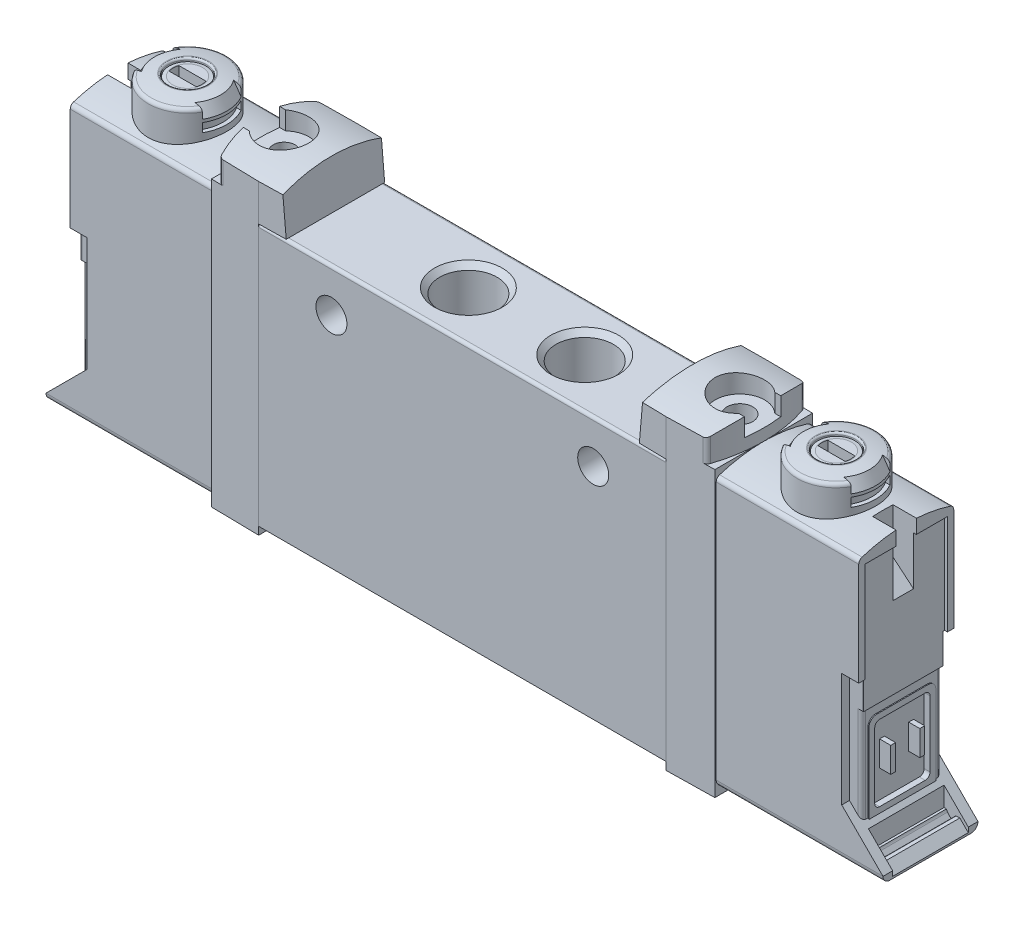
SolidWorks part; units mm, degrees
ref_plane "Front Plane" through (0, 0, 0) normal (0, 0, 1) x (1, 0, 0)
ref_plane "Top Plane" through (0, 0, 0) normal (0, 1, 0) x (1, 0, 0)
ref_plane "Right Plane" through (0, 0, 0) normal (1, 0, 0) x (0, 0, -1)
sketch "Sketch1" plane through (0, 0, 0) normal (1, 0, 0) x (0, 0, -1)
  line L0 (-5.125, 0) -> (5.125, 0)
  line L1 (5.125, 0) -> (5.125, 26.7)
  line L2 (4.825, 27) -> (-4.825, 27)
  line L3 (-5.125, 26.7) -> (-5.125, 0)
  arc A0 (5.125, 26.7) -> (4.825, 27) centre (4.825, 26.7) ccw
  arc A1 (-4.825, 27) -> (-5.125, 26.7) centre (-4.825, 26.7) ccw
extrude "Boss-Extrude1" add sketch "Sketch1" against normal blind 21 and the other way blind 21
sketch "Sketch2" plane through (0, 0, 0) normal (0, 0, 1) x (1, 0, 0)
  circle A0 centre (13.5, 22.6) radius 1.6
extrude "Cut-Extrude1" cut sketch "Sketch2" along normal blind 6 and the other way blind 6
sketch "Sketch3" plane through (0, 0, 0) normal (0, 0, 1) x (1, 0, 0)
  circle A0 centre (-13.5, 22.6) radius 1.6
extrude "Cut-Extrude2" cut sketch "Sketch3" along normal blind 6 and the other way blind 6
ref_plane "Plane1" through (0, 0, -0.005) normal (0, 0, 1) x (1, 0, 0)
ref_plane "Plane2" through (0, 0, -1.555) normal (0, 0, 1) x (1, 0, 0)
ref_plane "Plane3" through (0, 0, 1.545) normal (0, 0, 1) x (1, 0, 0)
ref_plane "Plane4" through (0, 0, 1.495) normal (0, 0, 1) x (1, 0, 0)
ref_plane "Plane5" through (0, 0, -2.205) normal (0, 0, 1) x (1, 0, 0)
sketch "Sketch4" plane through (0, 0, -0.005) normal (0, 0, 1) x (1, 0, 0)
  line L0 (12.5, 13.5) -> (14.6, 13.5)
  line L1 (14.6, 13.5) -> (14.6, 6.8)
  line L2 (14.6, 6.8) -> (15.4585, 6.8)
  line L3 (15.4585, 6.8) -> (15.4585, 0.5415)
  line L4 (15.4585, 0.5415) -> (16, 0)
  line L5 (16, 0) -> (12.5, 0)
  line L6 (12.5, 0) -> (12.5, 13.5)
  line L7 (12.5, 0) -> (12.5, 13.5) construction
sketch "Sketch5" plane through (0, 0, -0.005) normal (0, 0, 1) x (1, 0, 0)
  line L0 (1.5, 20.0124) -> (3.6, 18.8)
  line L1 (3.6, 18.8) -> (3.6, 6.8)
  line L2 (3.6, 6.8) -> (4.4585, 6.8)
  line L3 (4.4585, 6.8) -> (4.4585, 0.5415)
  line L4 (4.4585, 0.5415) -> (5, 0)
  line L5 (5, 0) -> (1.5, 0)
  line L6 (1.5, 0) -> (1.5, 20.0124)
  line L7 (1.5, 0) -> (1.5, 20.0124) construction
sketch "Sketch6" plane through (0, 0, -0.005) normal (0, 0, 1) x (1, 0, 0)
  line L0 (-9.5, 13.5) -> (-7.4, 13.5)
  line L1 (-7.4, 13.5) -> (-7.4, 6.8)
  line L2 (-7.4, 6.8) -> (-6.5415, 6.8)
  line L3 (-6.5415, 6.8) -> (-6.5415, 0.5415)
  line L4 (-6.5415, 0.5415) -> (-6, 0)
  line L5 (-6, 0) -> (-9.5, 0)
  line L6 (-9.5, 0) -> (-9.5, 13.5)
  line L7 (-9.5, 0) -> (-9.5, 13.5) construction
revolve "Cut-Revolve1" cut sketch "Sketch4" angle 360 about L7 reverse direction yes
cosmetic thread "Cosmetic Thread1" parameters "D1"=6, "D2"=7
revolve "Cut-Revolve2" cut sketch "Sketch5" angle 360 about L7 reverse direction yes
cosmetic thread "Cosmetic Thread2" parameters "D1"=6, "D2"=7
revolve "Cut-Revolve3" cut sketch "Sketch6" angle 360 about L7 reverse direction yes
cosmetic thread "Cosmetic Thread3" parameters "D1"=6, "D2"=7
hole_wizard "Hole1" positions "Sketch8" profile "Sketch7" legacy
sketch "Sketch8" plane through (0, 27, 0) normal (0, 1, 0) x (-1, 0, 0)
  point P0 (4.5, 0)
sketch "Sketch7" plane through (-4.5, 27, 0) normal (1, 0, 0) x (0, 0, 1)
  line L0 (0, 0) -> (0, 6.8)
  line L1 (0, 6.8) -> (2.9585, 6.8)
  line L2 (2.9585, 6.8) -> (2.9585, 0.5415)
  line L3 (2.9585, 0.5415) -> (3.5, 0)
  line L4 (3.5, 0) -> (0, 0)
  line L5 (0, -6.4453) -> (0, 115.525) construction
  line L6 (-2.9585, 0.5415) -> (-3.5, 0) construction
  dimension "Diameter" = 5.917
  dimension "Depth" = 6.8
  dimension "C-Sink Angle" = 90
  dimension "C-Sink Diameter" = 7
cosmetic thread "Cosmetic Thread4" parameters "D1"=6, "D2"=7
hole_wizard "Hole2" positions "Sketch10" profile "Sketch9" legacy
sketch "Sketch10" plane through (0, 27, 0) normal (0, 1, 0) x (-1, 0, 0)
  point P0 (-7.5, 0)
sketch "Sketch9" plane through (7.5, 27, 0) normal (1, 0, 0) x (0, 0, 1)
  line L0 (0, 0) -> (0, 6.8)
  line L1 (0, 6.8) -> (2.9585, 6.8)
  line L2 (2.9585, 6.8) -> (2.9585, 0.5415)
  line L3 (2.9585, 0.5415) -> (3.5, 0)
  line L4 (3.5, 0) -> (0, 0)
  line L5 (0, -6.4453) -> (0, 115.525) construction
  line L6 (-2.9585, 0.5415) -> (-3.5, 0) construction
  dimension "Diameter" = 5.917
  dimension "Depth" = 6.8
  dimension "C-Sink Angle" = 90
  dimension "C-Sink Diameter" = 7
cosmetic thread "Cosmetic Thread5" parameters "D1"=6, "D2"=7
ref_plane "Plane6" through (0, 20.2, 0) normal (0, 1, 0) x (-1, 0, 0)
hole_wizard "Hole3" positions "Sketch12" profile "Sketch11" legacy
sketch "Sketch12" plane through (0, 20.2, 0) normal (0, 1, 0) x (-1, 0, 0)
  point P0 (4.5, 1)
sketch "Sketch11" plane through (-4.5, 20.2, 1) normal (1, 0, 0) x (0, 0, 1)
  line L0 (0, 0) -> (0, 6.7)
  line L1 (0, 6.7) -> (1.5, 6.7)
  line L2 (1.5, 6.7) -> (1.5, 0)
  line L3 (1.5, 0) -> (0, 0)
  line L4 (0, 110) -> (0, -10) construction
  dimension "Diameter" = 3
  dimension "Depth" = 6.7
hole_wizard "Hole4" positions "Sketch14" profile "Sketch13" legacy
sketch "Sketch14" plane through (0, 20.2, 0) normal (0, 1, 0) x (-1, 0, 0)
  point P0 (-7.5, -1)
sketch "Sketch13" plane through (7.5, 20.2, -1) normal (1, 0, 0) x (0, 0, 1)
  line L0 (0, 0) -> (0, 6.7)
  line L1 (0, 6.7) -> (1.5, 6.7)
  line L2 (1.5, 6.7) -> (1.5, 0)
  line L3 (1.5, 0) -> (0, 0)
  line L4 (0, 110) -> (0, -10) construction
  dimension "Diameter" = 3
  dimension "Depth" = 6.7
ref_plane "Plane7" through (-15.16, 0, 0) normal (1, 0, 0) x (0, 0, -1)
ref_plane "Plane8" through (-8.25, 0, 0) normal (1, 0, 0) x (0, 0, -1)
ref_plane "Plane9" through (-0.95, 0, 0) normal (1, 0, 0) x (0, 0, -1)
ref_plane "Plane10" through (0, -0.8, 0) normal (0, 1, 0) x (-1, 0, 0)
sketch "Sketch15" plane through (0, -0.8, 0) normal (0, 1, 0) x (-1, 0, 0)
  line L0 (-21, 5.125) -> (-25.96, 5.0384)
  line L1 (-25.96, 5.0384) -> (-25.96, -5.0384)
  line L2 (-25.96, -5.0384) -> (-21, -5.125)
  line L3 (-21, -5.125) -> (-21, 5.125)
extrude "Boss-Extrude2" add sketch "Sketch15" along normal blind 32.5
ref_plane "Plane11" through (0, 27, 0) normal (0, 1, 0) x (-1, 0, 0)
sketch "Sketch16" plane through (0, 27, 0) normal (0, 1, 0) x (-1, 0, 0)
  line L0 (-18.21, 5.0763) -> (-21, 5.125)
  line L1 (-21, 5.125) -> (-21, -5.125)
  line L2 (-21, -5.125) -> (-18.21, -5.0763)
  line L3 (-18.21, -5.0763) -> (-18.21, 5.0763)
extrude "Boss-Extrude3" add sketch "Sketch16" along normal blind 4.7
sketch "Sketch17" plane through (0, 0, 0) normal (1, 0, 0) x (0, 0, -1)
  line L0 (-5.125, 37) -> (-5.125, 30.7973)
  line L1 (5.125, 30.7973) -> (5.125, 37)
  line L2 (5.125, 37) -> (-5.125, 37)
  arc A0 (-5.125, 30.7973) -> (5.125, 30.7973) centre (0, 16.7) cw
ref_plane "Plane12" through (0, 28.5, 0) normal (0, 1, 0) x (-1, 0, 0)
sketch "Sketch18" plane through (0, 28.5, 0) normal (0, 1, 0) x (-1, 0, 0)
  line L0 (-21, 5.125) -> (-21, 6.125)
  line L1 (-21, 6.125) -> (-31, 6.125)
  line L2 (-31, 6.125) -> (-31, -6.125)
  line L3 (-31, -6.125) -> (-21, -6.125)
  line L4 (-21, -6.125) -> (-21, -5.125)
  line L5 (-21, -5.125) -> (-24.7331, -5.0598)
  line L6 (-24.7331, 5.0598) -> (-21, 5.125)
  arc A0 (-24.7331, -5.0598) -> (-25.199, -4.7172) centre (-24.7243, -4.5599) cw
  arc A1 (-25.199, -4.7172) -> (-25.199, 4.7172) centre (-10.96, 0) cw
  arc A2 (-25.199, 4.7172) -> (-24.7331, 5.0598) centre (-24.7243, 4.5599) cw
extrude "Cut-Extrude3" cut sketch "Sketch18" along normal blind 5
sketch "Sketch19" plane through (0, 0, 0) normal (0, 0, 1) x (1, 0, 0)
  line L0 (13.21, 27) -> (18.21, 27)
  line L1 (18.21, 27) -> (18.6474, 32)
  line L2 (18.6474, 32) -> (13.21, 32)
  line L3 (13.21, 32) -> (13.21, 27)
extrude "Cut-Extrude4" cut sketch "Sketch19" along normal blind 6 and the other way blind 6
ref_plane "Plane13" through (25.96, 0, 0) normal (1, 0, 0) x (0, 0, -1)
sketch "Sketch20" plane through (25.96, 0, 0) normal (1, 0, 0) x (0, 0, -1)
  line L0 (-4.9, 27.3163) -> (-4.9, 0.7)
  line L1 (-4.2, 0) -> (4.2, 0)
  line L2 (4.9, 0.7) -> (4.9, 27.3163)
  arc A0 (-4.9, 0.7) -> (-4.2, 0) centre (-4.2, 0.7) ccw
  arc A1 (4.2, 0) -> (4.9, 0.7) centre (4.2, 0.7) ccw
  arc A2 (4.9, 27.3163) -> (4.5517, 27.7927) centre (4.4, 27.3163) ccw
  arc A3 (4.5517, 27.7927) -> (-4.5517, 27.7927) centre (0, 13.5) ccw
  arc A4 (-4.5517, 27.7927) -> (-4.9, 27.3163) centre (-4.4, 27.3163) ccw
extrude "Boss-Extrude4" add sketch "Sketch20" along normal blind 17.2
sketch "Sketch21" plane through (0, 0, 0) normal (0, 0, 1) x (1, 0, 0)
  line L0 (38.9067, 16.7) -> (38.9067, 4.9533)
  line L1 (38.9067, 4.9533) -> (43.16, 0.7)
  line L2 (43.16, 0.7) -> (43.16, 30)
  line L3 (43.16, 30) -> (40.66, 30)
  line L4 (40.66, 30) -> (40.66, 16.7)
  line L5 (40.66, 16.7) -> (38.9067, 16.7)
extrude "Cut-Extrude5" cut sketch "Sketch21" along normal blind 6 and the other way blind 6
ref_plane "Plane14" through (0, 13.6, 0) normal (0, 1, 0) x (-1, 0, 0)
sketch "Sketch22" plane through (0, 13.6, 0) normal (0, 1, 0) x (-1, 0, 0)
  line L0 (-38.16, 4.1) -> (-39.76, 4.1)
  line L1 (-40.16, 3.7) -> (-40.16, -3.7)
  line L2 (-39.76, -4.1) -> (-38.16, -4.1)
  line L3 (-38.16, -4.1) -> (-38.16, 4.1)
  arc A0 (-39.76, 4.1) -> (-40.16, 3.7) centre (-39.76, 3.7) ccw
  arc A1 (-40.16, -3.7) -> (-39.76, -4.1) centre (-39.76, -3.7) ccw
extrude "Boss-Extrude5" add sketch "Sketch22" against normal blind 12
sketch "Sketch23" plane through (0, 13.6, 0) normal (0, 1, 0) x (-1, 0, 0)
  line L0 (-37.66, 4.1) -> (-40.26, 4.1)
  line L1 (-40.66, 3.7) -> (-40.66, -3.7)
  line L2 (-40.26, -4.1) -> (-37.66, -4.1)
  line L3 (-37.66, -4.1) -> (-37.66, 4.1)
  arc A0 (-40.26, 4.1) -> (-40.66, 3.7) centre (-40.26, 3.7) ccw
  arc A1 (-40.66, -3.7) -> (-40.26, -4.1) centre (-40.26, -3.7) ccw
extrude "Boss-Extrude6" add sketch "Sketch23" along normal blind 3.1
ref_plane "Plane15" through (40.16, 0, 0) normal (1, 0, 0) x (0, 0, -1)
sketch "Sketch24" plane through (40.16, 0, 0) normal (1, 0, 0) x (0, 0, -1)
  line L0 (-3.45, 0) -> (3.45, 0)
  line L1 (3.45, 0) -> (3.45, 11.8)
  line L2 (2.65, 12.6) -> (-2.65, 12.6)
  line L3 (-3.45, 11.8) -> (-3.45, 0)
  arc A0 (3.45, 11.8) -> (2.65, 12.6) centre (2.65, 11.8) ccw
  arc A1 (-2.65, 12.6) -> (-3.45, 11.8) centre (-2.65, 11.8) ccw
extrude "Boss-Extrude7" add sketch "Sketch24" along normal blind 0.1
sketch "Sketch25" plane through (40.16, 0, 0) normal (1, 0, 0) x (0, 0, -1)
  line L0 (-2.85, 11.5) -> (-2.85, 4.7)
  line L1 (-2.35, 4.2) -> (2.35, 4.2)
  line L2 (2.85, 4.7) -> (2.85, 11.5)
  line L3 (2.35, 12) -> (-2.35, 12)
  arc A0 (-2.85, 4.7) -> (-2.35, 4.2) centre (-2.35, 4.7) ccw
  arc A1 (2.35, 4.2) -> (2.85, 4.7) centre (2.35, 4.7) ccw
  arc A2 (2.85, 11.5) -> (2.35, 12) centre (2.35, 11.5) ccw
  arc A3 (-2.35, 12) -> (-2.85, 11.5) centre (-2.35, 11.5) ccw
extrude "Cut-Extrude6" cut sketch "Sketch25" along normal blind 0.5 and the other way blind 0.5
ref_plane "Plane16" through (0, 9.65, 0) normal (0, 1, 0) x (-1, 0, 0)
sketch "Sketch26" plane through (0, 9.65, 0) normal (0, 1, 0) x (-1, 0, 0)
  line L0 (-35.81, -1.75) -> (-35.81, 1.75)
  line L1 (-35.81, 1.75) -> (-40.81, 1.75)
  line L2 (-40.81, 1.75) -> (-40.81, 1.25)
  line L3 (-40.81, 1.25) -> (-36.31, 1.25)
  line L4 (-36.31, 1.25) -> (-36.31, -1.25)
  line L5 (-36.31, -1.25) -> (-40.81, -1.25)
  line L6 (-40.81, -1.25) -> (-40.81, -1.75)
  line L7 (-40.81, -1.75) -> (-35.81, -1.75)
extrude "Boss-Extrude8" add sketch "Sketch26" against normal blind 2.6
sketch "Sketch27" plane through (0, 0, 0) normal (0, 0, 1) x (1, 0, 0)
  line L0 (23.5, 29.7) -> (24.825, 29.7)
  line L1 (24.825, 29.7) -> (24.625, -0.8)
  line L2 (24.625, -0.8) -> (23.5, -0.8)
  line L3 (23.5, -0.8) -> (23.5, 29.7)
  line L4 (23.5, -0.8) -> (23.5, 29.7) construction
revolve "Cut-Revolve4" cut sketch "Sketch27" angle 360 about L4 reverse direction yes
ref_plane "Plane17" through (0, 29.7, 0) normal (0, 1, 0) x (-1, 0, 0)
sketch "Sketch28" plane through (0, 29.7, 0) normal (0, 1, 0) x (-1, 0, 0)
  line L0 (-25.2283, 1.875) -> (-27, 1.875)
  line L1 (-27, 1.875) -> (-27, -1.875)
  line L2 (-27, -1.875) -> (-25.2283, -1.875)
  arc A0 (-25.2283, -1.875) -> (-25.2283, 1.875) centre (-23.5, 0) ccw
extrude "Cut-Extrude7" cut sketch "Sketch28" along normal blind 3
ref_plane "Plane18" through (0, -0.8, 0) normal (0, 1, 0) x (-1, 0, 0)
sketch "Sketch29" plane through (0, -0.8, 0) normal (0, 1, 0) x (-1, 0, 0)
  line L0 (25.96, -5.0384) -> (25.96, 5.0384)
  line L1 (25.96, 5.0384) -> (21, 5.125)
  line L2 (21, 5.125) -> (21, -5.125)
  line L3 (21, -5.125) -> (25.96, -5.0384)
extrude "Boss-Extrude9" add sketch "Sketch29" along normal blind 32.5
sketch "Sketch30" plane through (0, 27, 0) normal (0, 1, 0) x (-1, 0, 0)
  line L0 (21, -5.125) -> (21, 5.125)
  line L1 (21, 5.125) -> (18.21, 5.0763)
  line L2 (18.21, 5.0763) -> (18.21, -5.0763)
  line L3 (18.21, -5.0763) -> (21, -5.125)
extrude "Boss-Extrude10" add sketch "Sketch30" along normal blind 4.7
extrude "Cut-Extrude8" cut sketch "Sketch17" along normal blind 32 and the other way blind 32
sketch "Sketch31" plane through (0, 29.7, 0) normal (0, 1, 0) x (-1, 0, 0)
  line L0 (27, -1.875) -> (27, 1.875)
  line L1 (27, 1.875) -> (25.2283, 1.875)
  line L2 (25.2283, -1.875) -> (27, -1.875)
  arc A0 (25.2283, 1.875) -> (25.2283, -1.875) centre (23.5, 0) ccw
extrude "Cut-Extrude9" cut sketch "Sketch31" along normal blind 2
hole_wizard "Hole5" positions "Sketch33" profile "Sketch32" legacy
sketch "Sketch33" plane through (0, 29.7, 0) normal (0, 1, 0) x (-1, 0, 0)
  point P0 (23.5, 0)
sketch "Sketch32" plane through (-23.5, 29.7, 0) normal (1, 0, 0) x (0, 0, 1)
  line L0 (0, 0) -> (0, 30.5)
  line L1 (0, 30.5) -> (1.325, 30.5)
  line L2 (1.325, 30.5) -> (1.125, 0)
  line L3 (1.125, 0) -> (0, 0)
  line L4 (0, 110) -> (0, -10) construction
  dimension "Minor Diameter" = 2.65
  dimension "Depth" = 30.5
  dimension "Major Diameter" = 2.25
sketch "Sketch34" plane through (0, 0, 0) normal (0, 0, 1) x (1, 0, 0)
  line L0 (-18.6474, 32) -> (-18.21, 27)
  line L1 (-18.21, 27) -> (-13.21, 27)
  line L2 (-13.21, 27) -> (-13.21, 32)
  line L3 (-13.21, 32) -> (-18.6474, 32)
extrude "Cut-Extrude10" cut sketch "Sketch34" along normal blind 6 and the other way blind 6
sketch "Sketch35" plane through (0, 28.5, 0) normal (0, 1, 0) x (-1, 0, 0)
  line L0 (31, -6.125) -> (31, 6.125)
  line L1 (31, 6.125) -> (21, 6.125)
  line L2 (21, 6.125) -> (21, 5.125)
  line L3 (21, 5.125) -> (24.7331, 5.0598)
  line L4 (24.7331, -5.0598) -> (21, -5.125)
  line L5 (21, -5.125) -> (21, -6.125)
  line L6 (21, -6.125) -> (31, -6.125)
  arc A0 (24.7331, 5.0598) -> (25.199, 4.7172) centre (24.7243, 4.5599) cw
  arc A1 (25.199, 4.7172) -> (25.199, -4.7172) centre (10.96, 0) cw
  arc A2 (25.199, -4.7172) -> (24.7331, -5.0598) centre (24.7243, -4.5599) cw
extrude "Cut-Extrude11" cut sketch "Sketch35" along normal blind 5
ref_plane "Plane19" through (-25.96, 0, 0) normal (1, 0, 0) x (0, 0, -1)
sketch "Sketch36" plane through (-25.96, 0, 0) normal (1, 0, 0) x (0, 0, -1)
  line L0 (-4.9, 27.3163) -> (-4.9, 0.7)
  line L1 (-4.2, 0) -> (4.2, 0)
  line L2 (4.9, 0.7) -> (4.9, 27.3163)
  arc A0 (-4.9, 0.7) -> (-4.2, 0) centre (-4.2, 0.7) ccw
  arc A1 (4.2, 0) -> (4.9, 0.7) centre (4.2, 0.7) ccw
  arc A2 (4.9, 27.3163) -> (4.5517, 27.7927) centre (4.4, 27.3163) ccw
  arc A3 (4.5517, 27.7927) -> (-4.5517, 27.7927) centre (0, 13.5) ccw
  arc A4 (-4.5517, 27.7927) -> (-4.9, 27.3163) centre (-4.4, 27.3163) ccw
extrude "Boss-Extrude11" add sketch "Sketch36" against normal blind 17.2
sketch "Sketch37" plane through (0, 0, 0) normal (0, 0, 1) x (1, 0, 0)
  line L0 (-43.16, 0.7) -> (-38.9067, 4.9533)
  line L1 (-38.9067, 4.9533) -> (-38.9067, 16.7)
  line L2 (-38.9067, 16.7) -> (-40.66, 16.7)
  line L3 (-40.66, 16.7) -> (-40.66, 30)
  line L4 (-40.66, 30) -> (-43.16, 30)
  line L5 (-43.16, 30) -> (-43.16, 0.7)
extrude "Cut-Extrude12" cut sketch "Sketch37" along normal blind 6 and the other way blind 6
sketch "Sketch38" plane through (0, 13.6, 0) normal (0, 1, 0) x (-1, 0, 0)
  line L0 (39.76, 4.1) -> (38.16, 4.1)
  line L1 (38.16, 4.1) -> (38.16, -4.1)
  line L2 (38.16, -4.1) -> (39.76, -4.1)
  line L3 (40.16, -3.7) -> (40.16, 3.7)
  arc A0 (40.16, 3.7) -> (39.76, 4.1) centre (39.76, 3.7) ccw
  arc A1 (39.76, -4.1) -> (40.16, -3.7) centre (39.76, -3.7) ccw
extrude "Boss-Extrude12" add sketch "Sketch38" against normal blind 12
sketch "Sketch39" plane through (0, 13.6, 0) normal (0, 1, 0) x (-1, 0, 0)
  line L0 (40.26, 4.1) -> (37.66, 4.1)
  line L1 (37.66, 4.1) -> (37.66, -4.1)
  line L2 (37.66, -4.1) -> (40.26, -4.1)
  line L3 (40.66, -3.7) -> (40.66, 3.7)
  arc A0 (40.66, 3.7) -> (40.26, 4.1) centre (40.26, 3.7) ccw
  arc A1 (40.26, -4.1) -> (40.66, -3.7) centre (40.26, -3.7) ccw
extrude "Boss-Extrude13" add sketch "Sketch39" along normal blind 3.1
ref_plane "Plane20" through (-40.16, 0, 0) normal (1, 0, 0) x (0, 0, -1)
sketch "Sketch40" plane through (-40.16, 0, 0) normal (1, 0, 0) x (0, 0, -1)
  line L0 (-3.45, 0) -> (3.45, 0)
  line L1 (3.45, 0) -> (3.45, 11.8)
  line L2 (2.65, 12.6) -> (-2.65, 12.6)
  line L3 (-3.45, 11.8) -> (-3.45, 0)
  arc A0 (3.45, 11.8) -> (2.65, 12.6) centre (2.65, 11.8) ccw
  arc A1 (-2.65, 12.6) -> (-3.45, 11.8) centre (-2.65, 11.8) ccw
extrude "Boss-Extrude14" add sketch "Sketch40" against normal blind 0.1
sketch "Sketch41" plane through (-40.16, 0, 0) normal (1, 0, 0) x (0, 0, -1)
  line L0 (-2.85, 11.5) -> (-2.85, 4.7)
  line L1 (-2.35, 4.2) -> (2.35, 4.2)
  line L2 (2.85, 4.7) -> (2.85, 11.5)
  line L3 (2.35, 12) -> (-2.35, 12)
  arc A0 (-2.85, 4.7) -> (-2.35, 4.2) centre (-2.35, 4.7) ccw
  arc A1 (2.35, 4.2) -> (2.85, 4.7) centre (2.35, 4.7) ccw
  arc A2 (2.85, 11.5) -> (2.35, 12) centre (2.35, 11.5) ccw
  arc A3 (-2.35, 12) -> (-2.85, 11.5) centre (-2.35, 11.5) ccw
extrude "Cut-Extrude13" cut sketch "Sketch41" along normal blind 0.5 and the other way blind 0.5
sketch "Sketch42" plane through (0, 9.65, 0) normal (0, 1, 0) x (-1, 0, 0)
  line L0 (40.81, 1.75) -> (35.81, 1.75)
  line L1 (35.81, 1.75) -> (35.81, -1.75)
  line L2 (35.81, -1.75) -> (40.81, -1.75)
  line L3 (40.81, -1.75) -> (40.81, -1.25)
  line L4 (40.81, -1.25) -> (36.31, -1.25)
  line L5 (36.31, -1.25) -> (36.31, 1.25)
  line L6 (36.31, 1.25) -> (40.81, 1.25)
  line L7 (40.81, 1.25) -> (40.81, 1.75)
extrude "Boss-Extrude15" add sketch "Sketch42" against normal blind 2.6
sketch "Sketch43" plane through (0, 0, 0) normal (0, 0, 1) x (1, 0, 0)
  line L0 (33.46, 31.665) -> (37.51, 31.665)
  line L1 (37.51, 31.665) -> (37.51, 26.365)
  line L2 (37.51, 26.365) -> (33.46, 26.365)
  line L3 (33.46, 26.365) -> (33.46, 31.665)
  line L4 (33.46, 26.365) -> (33.46, 31.665) construction
revolve "Revolve1" add sketch "Sketch43" angle 360 about L4 reverse direction yes
sketch "Sketch44" plane through (0, 0, 0) normal (0, 0, 1) x (1, 0, 0)
  line L0 (-33.46, 31.665) -> (-29.41, 31.665)
  line L1 (-29.41, 31.665) -> (-29.41, 26.365)
  line L2 (-29.41, 26.365) -> (-33.46, 26.365)
  line L3 (-33.46, 26.365) -> (-33.46, 31.665)
  line L4 (-33.46, 26.365) -> (-33.46, 31.665) construction
revolve "Revolve2" add sketch "Sketch44" angle 360 about L4 reverse direction yes
sketch "Sketch45" plane through (0, 0, 0) normal (0, 0, 1) x (1, 0, 0)
  line L0 (33.46, 32.365) -> (38.46, 32.365)
  line L1 (38.46, 32.365) -> (38.46, 28.865)
  line L2 (38.46, 28.865) -> (37.51, 28.865)
  line L3 (37.51, 28.865) -> (37.51, 30.9614)
  line L4 (35.41, 31.468) -> (35.41, 30.295)
  line L5 (35.41, 30.295) -> (33.46, 30.295)
  line L6 (33.46, 30.295) -> (33.46, 32.365)
  line L7 (33.46, 26.365) -> (33.46, 32.365) construction
  arc A0 (37.51, 30.9614) -> (37.21, 31.3487) centre (37.11, 30.9614) ccw
  arc A1 (37.21, 31.3487) -> (35.6391, 31.6659) centre (33.46, 16.825) ccw
  arc A2 (35.6391, 31.6659) -> (35.41, 31.468) centre (35.61, 31.468) ccw
sketch "Sketch46" plane through (0, 0, 0) normal (0, 0, 1) x (1, 0, 0)
  line L0 (33.46, 31.41) -> (35.0042, 31.41)
  line L1 (35.0042, 31.41) -> (35.36, 31.36)
  line L2 (35.36, 31.36) -> (35.36, 29.71)
  line L3 (35.86, 29.21) -> (36.01, 29.21)
  line L4 (36.01, 29.21) -> (36.01, 25.41)
  line L5 (36.01, 25.41) -> (33.46, 25.41)
  line L6 (33.46, 25.41) -> (33.46, 31.41)
  line L7 (33.46, 25.41) -> (33.46, 31.41) construction
  arc A0 (35.36, 29.71) -> (35.86, 29.21) centre (35.86, 29.71) ccw
ref_plane "Plane21" through (0, 29.1, 0) normal (0, 1, 0) x (-1, 0, 0)
sketch "Sketch47" plane through (0, 29.1, 0) normal (0, 1, 0) x (-1, 0, 0)
  line L0 (-28.8774, -2) -> (-30.7105, -2)
  line L1 (-30.7105, 2) -> (-28.8774, 2)
  line L2 (-38.0426, 2) -> (-36.2095, 2)
  line L3 (-36.2095, -2) -> (-38.0426, -2)
  circle A0 centre (-33.46, 0) radius 6
  arc A1 (-30.7105, -2) -> (-30.7105, 2) centre (-33.46, 0) ccw
  arc A2 (-28.8774, 2) -> (-38.0426, 2) centre (-33.46, 0) ccw
  arc A3 (-36.2095, 2) -> (-36.2095, -2) centre (-33.46, 0) ccw
  arc A4 (-38.0426, -2) -> (-28.8774, -2) centre (-33.46, 0) ccw
extrude "Cut-Extrude14" cut sketch "Sketch47" along normal blind 3
sketch "Sketch48" plane through (0, 29.1, 0) normal (0, 1, 0) x (-1, 0, 0)
  line L0 (38.0426, -2) -> (36.2095, -2)
  line L1 (36.2095, 2) -> (38.0426, 2)
  line L2 (28.8774, 2) -> (30.7105, 2)
  line L3 (30.7105, -2) -> (28.8774, -2)
  circle A0 centre (33.46, 0) radius 6
  arc A1 (36.2095, -2) -> (36.2095, 2) centre (33.46, 0) ccw
  arc A2 (38.0426, 2) -> (28.8774, 2) centre (33.46, 0) ccw
  arc A3 (30.7105, 2) -> (30.7105, -2) centre (33.46, 0) ccw
  arc A4 (28.8774, -2) -> (38.0426, -2) centre (33.46, 0) ccw
extrude "Cut-Extrude15" cut sketch "Sketch48" along normal blind 3
sketch "Sketch49" plane through (0, 0, 0) normal (0, 0, 1) x (1, 0, 0)
  line L0 (36.86, 26.365) -> (37.51, 26.365)
  line L1 (37.51, 26.365) -> (37.51, 29.115)
  line L2 (37.51, 29.115) -> (37.11, 29.115)
  line L3 (37.11, 29.115) -> (37.11, 30.015)
  line L4 (37.11, 30.015) -> (37.51, 30.015)
  line L5 (37.51, 30.015) -> (37.51, 30.315)
  line L6 (37.51, 30.315) -> (36.86, 31.4408)
  line L7 (36.86, 31.4408) -> (36.86, 26.365)
  line L8 (33.46, 26.365) -> (33.46, 31.665) construction
revolve "Revolve3" add sketch "Sketch49" angle 360 about L8 reverse direction yes
sketch "Sketch50" plane through (0, 0, 0) normal (0, 0, 1) x (1, 0, 0)
  line L0 (-30.06, 26.365) -> (-29.41, 26.365)
  line L1 (-29.41, 26.365) -> (-29.41, 29.115)
  line L2 (-29.41, 29.115) -> (-29.81, 29.115)
  line L3 (-29.81, 29.115) -> (-29.81, 30.015)
  line L4 (-29.81, 30.015) -> (-29.41, 30.015)
  line L5 (-29.41, 30.015) -> (-29.41, 30.315)
  line L6 (-29.41, 30.315) -> (-30.06, 31.4408)
  line L7 (-30.06, 31.4408) -> (-30.06, 26.365)
  line L8 (-33.46, 26.365) -> (-33.46, 31.665) construction
revolve "Revolve4" add sketch "Sketch50" angle 360 about L8 reverse direction yes
revolve "Cut-Revolve5" cut sketch "Sketch45" angle 360 about L7 reverse direction yes
sketch "Sketch51" plane through (0, 0, 0) normal (0, 0, 1) x (1, 0, 0)
  line L0 (-33.46, 32.365) -> (-28.46, 32.365)
  line L1 (-28.46, 32.365) -> (-28.46, 28.865)
  line L2 (-28.46, 28.865) -> (-29.41, 28.865)
  line L3 (-29.41, 28.865) -> (-29.41, 30.9614)
  line L4 (-31.51, 31.468) -> (-31.51, 30.295)
  line L5 (-31.51, 30.295) -> (-33.46, 30.295)
  line L6 (-33.46, 30.295) -> (-33.46, 32.365)
  line L7 (-33.46, 26.365) -> (-33.46, 32.365) construction
  arc A0 (-29.41, 30.9614) -> (-29.71, 31.3487) centre (-29.81, 30.9614) ccw
  arc A1 (-29.71, 31.3487) -> (-31.2809, 31.6659) centre (-33.46, 16.825) ccw
  arc A2 (-31.2809, 31.6659) -> (-31.51, 31.468) centre (-31.31, 31.468) ccw
revolve "Cut-Revolve6" cut sketch "Sketch51" angle 360 about L7 reverse direction yes
revolve "Revolve5" add sketch "Sketch46" angle 360 about L7 reverse direction yes
sketch "Sketch52" plane through (0, 0, 0) normal (0, 0, 1) x (1, 0, 0)
  line L0 (-33.46, 31.41) -> (-31.9158, 31.41)
  line L1 (-31.9158, 31.41) -> (-31.56, 31.36)
  line L2 (-31.56, 31.36) -> (-31.56, 29.71)
  line L3 (-31.06, 29.21) -> (-30.91, 29.21)
  line L4 (-30.91, 29.21) -> (-30.91, 25.41)
  line L5 (-30.91, 25.41) -> (-33.46, 25.41)
  line L6 (-33.46, 25.41) -> (-33.46, 31.41)
  line L7 (-33.46, 25.41) -> (-33.46, 31.41) construction
  arc A0 (-31.56, 29.71) -> (-31.06, 29.21) centre (-31.06, 29.71) ccw
revolve "Revolve6" add sketch "Sketch52" angle 360 about L7 reverse direction yes
ref_plane "Plane22" through (0, 31.41, 0) normal (0, 1, 0) x (-1, 0, 0)
sketch "Sketch53" plane through (0, 31.41, 0) normal (0, 1, 0) x (-1, 0, 0)
  line L0 (-32.067, 0.5) -> (-34.853, 0.5)
  line L1 (-34.853, -0.5) -> (-32.067, -0.5)
  arc A0 (-32.067, -0.5) -> (-32.067, 0.5) centre (-33.46, 0) ccw
  arc A1 (-34.853, 0.5) -> (-34.853, -0.5) centre (-33.46, 0) ccw
extrude "Cut-Extrude16" cut sketch "Sketch53" against normal blind 2.15
sketch "Sketch54" plane through (0, 31.41, 0) normal (0, 1, 0) x (-1, 0, 0)
  line L0 (34.853, 0.5) -> (32.067, 0.5)
  line L1 (32.067, -0.5) -> (34.853, -0.5)
  arc A0 (34.853, -0.5) -> (34.853, 0.5) centre (33.46, 0) ccw
  arc A1 (32.067, 0.5) -> (32.067, -0.5) centre (33.46, 0) ccw
extrude "Cut-Extrude17" cut sketch "Sketch54" against normal blind 2.15
ref_plane "Plane23" through (0, 0, -1.605) normal (0, 0, 1) x (1, 0, 0)
ref_plane "Plane24" through (0, 17.4, 0) normal (0, 1, 0) x (-1, 0, 0)
sketch "Sketch55" plane through (0, 0, 0) normal (0, 0, 1) x (1, 0, 0)
  line L0 (40.66, 4.2) -> (40.66, 1.2)
  line L1 (40.66, 1.2) -> (42.16, 1.2)
  line L2 (42.16, 1.2) -> (43.16, 0.2)
  line L3 (43.16, 0.2) -> (43.16, 4.2)
  line L4 (43.16, 4.2) -> (40.66, 4.2)
extrude "Cut-Extrude18" cut sketch "Sketch55" along normal blind 3.9 and the other way blind 3.9
sketch "Sketch56" plane through (0, 0, 0) normal (0, 0, 1) x (1, 0, 0)
  line L0 (-43.16, 0.2) -> (-42.16, 1.2)
  line L1 (-42.16, 1.2) -> (-40.66, 1.2)
  line L2 (-40.66, 1.2) -> (-40.66, 4.2)
  line L3 (-40.66, 4.2) -> (-43.16, 4.2)
  line L4 (-43.16, 4.2) -> (-43.16, 0.2)
extrude "Cut-Extrude19" cut sketch "Sketch56" along normal blind 3.9 and the other way blind 3.9
ref_plane "Plane25" through (0, 1.2, 0) normal (0, 1, 0) x (-1, 0, 0)
sketch "Sketch57" plane through (0, 0, 0) normal (0, 0, 1) x (1, 0, 0)
  line L0 (38.256, 23.774) -> (45.756, 17.4808)
  line L1 (45.756, 17.4808) -> (45.756, 28.534)
  line L2 (45.756, 28.534) -> (38.256, 28.534)
  line L3 (38.256, 28.534) -> (38.256, 23.774)
extrude "Cut-Extrude20" cut sketch "Sketch57" along normal blind 1.05 and the other way blind 1.05
sketch "Sketch58" plane through (0, 0, 0) normal (0, 0, 1) x (1, 0, 0)
  line L0 (-45.756, 17.4808) -> (-38.256, 23.774)
  line L1 (-38.256, 23.774) -> (-38.256, 28.534)
  line L2 (-38.256, 28.534) -> (-45.756, 28.534)
  line L3 (-45.756, 28.534) -> (-45.756, 17.4808)
extrude "Cut-Extrude21" cut sketch "Sketch58" along normal blind 1.05 and the other way blind 1.05
sketch "Sketch59" plane through (0, 0, 0) normal (0, 0, 1) x (1, 0, 0)
  line L0 (-43.2, 0.2) -> (-42.2, 1.2)
  line L1 (-42.2, 1.2) -> (-40.5, 1.2)
  line L2 (-40.5, 1.2) -> (-40.5, 4.2)
  line L3 (-40.5, 4.2) -> (-43.2, 4.2)
  line L4 (-43.2, 4.2) -> (-43.2, 0.2)
extrude "Cut-Extrude22" cut sketch "Sketch59" along normal blind 3.9 and the other way blind 3.9
sketch "Sketch60" plane through (0, 0, 0) normal (0, 0, 1) x (1, 0, 0)
  line L0 (41.0199, 0.9693) -> (41.5043, 0.412)
  line L1 (41.7205, 0.3157) -> (41.8612, 0.3181)
  line L2 (41.9556, 0.4457) -> (41.8153, 0.9349)
  line L3 (41.9079, 1.0624) -> (45.86, 1.2004)
  line L4 (45.86, 1.2004) -> (45.86, 1.9535)
  line L5 (45.86, 1.9535) -> (41.3798, 1.797)
  arc A0 (41.3798, 1.797) -> (41.0199, 0.9693) centre (41.3972, 1.2973) ccw
  arc A1 (41.5043, 0.412) -> (41.7205, 0.3157) centre (41.7157, 0.5957) ccw
  arc A2 (41.8612, 0.3181) -> (41.9556, 0.4457) centre (41.8594, 0.4181) ccw
  arc A3 (41.8153, 0.9349) -> (41.9079, 1.0624) centre (41.9114, 0.9625) cw
extrude "Cut-Extrude23" cut sketch "Sketch60" along normal blind 3.9 and the other way blind 3.9
sketch "Sketch61" plane through (0, 0, 0) normal (0, 0, 1) x (1, 0, 0)
  line L0 (-45.86, 1.2004) -> (-41.9079, 1.0624)
  line L1 (-41.8153, 0.9349) -> (-41.9556, 0.4457)
  line L2 (-41.8612, 0.3181) -> (-41.7205, 0.3157)
  line L3 (-41.5043, 0.412) -> (-41.0199, 0.9693)
  line L4 (-41.3798, 1.797) -> (-45.86, 1.9535)
  line L5 (-45.86, 1.9535) -> (-45.86, 1.2004)
  arc A0 (-41.9079, 1.0624) -> (-41.8153, 0.9349) centre (-41.9114, 0.9625) cw
  arc A1 (-41.9556, 0.4457) -> (-41.8612, 0.3181) centre (-41.8594, 0.4181) ccw
  arc A2 (-41.7205, 0.3157) -> (-41.5043, 0.412) centre (-41.7157, 0.5957) ccw
  arc A3 (-41.0199, 0.9693) -> (-41.3798, 1.797) centre (-41.3972, 1.2973) ccw
extrude "Cut-Extrude24" cut sketch "Sketch61" along normal blind 3.9 and the other way blind 3.9
ref_plane "Plane26" through (0, 31.66, 0) normal (0, 1, 0) x (-1, 0, 0)
ref_plane "Plane27" through (45.896, 0, 0) normal (1, 0, 0) x (0, 0, -1)
ref_plane "Plane28" through (-45.896, 0, 0) normal (1, 0, 0) x (0, 0, -1)
ref_plane "Plane29" through (43.16, 0, 0) normal (1, 0, 0) x (0, 0, -1)
sketch "Sketch62" plane through (43.16, 0, 0) normal (1, 0, 0) x (0, 0, -1)
  line L0 (-4.25, 27.012) -> (-4.25, 13.012)
  line L1 (-4.25, 13.012) -> (4.25, 13.012)
  line L2 (4.25, 13.012) -> (4.25, 27.012)
  line L3 (4.25, 27.012) -> (-4.25, 27.012)
extrude "Cut-Extrude25" cut sketch "Sketch62" against normal blind 2.8
ref_plane "Plane30" through (-43.16, 0, 0) normal (1, 0, 0) x (0, 0, -1)
sketch "Sketch63" plane through (-43.16, 0, 0) normal (1, 0, 0) x (0, 0, -1)
  line L0 (-4.25, 27.012) -> (-4.25, 13.012)
  line L1 (-4.25, 13.012) -> (4.25, 13.012)
  line L2 (4.25, 13.012) -> (4.25, 27.012)
  line L3 (4.25, 27.012) -> (-4.25, 27.012)
extrude "Cut-Extrude26" cut sketch "Sketch63" along normal blind 2.8
ref_plane "DICHTUNG XY" through (0, 0, 0) normal (0, 1, 0) x (-1, 0, 0)
ref_plane "DICHTUNG XZ" through (0, 0, 0) normal (0, 0, 1) x (1, 0, 0)
ref_plane "DICHTUNG YZ" through (1.5, 0, 0) normal (1, 0, 0) x (0, 0, -1)
ref_axis "DICHTUNG X" through (-80.9, 0, 0) along (1, 0, 0)
ref_axis "DICHTUNG Y" through (1.5, 0, 50) along (0, 0, -1)
ref_axis "DICHTUNG Z" through (1.5, 50, 0) along (0, -1, 0)
sketch3d "DICHTUNG"
  point P0 (1.5, 0, 0)
ref_plane "GEHAUSE XY" through (0, 0, 0) normal (0, 1, 0) x (-1, 0, 0)
ref_plane "GEHAUSE XZ" through (0, 0, 0) normal (0, 0, 1) x (1, 0, 0)
ref_plane "GEHAUSE YZ" through (0, 0, 0) normal (1, 0, 0) x (0, 0, -1)
ref_axis "GEHAUSE X" through (-80.9, 0, 0) along (1, 0, 0)
ref_axis "GEHAUSE Y" through (0, 0, 50) along (0, 0, -1)
ref_axis "GEHAUSE Z" through (0, 50, 0) along (0, -1, 0)
sketch3d "GEHAUSE"
  point P0 (0, 0, 0)
ref_plane "QS1 XY" through (0, 27, 0) normal (0, 1, 0) x (-1, 0, 0)
ref_plane "QS1 XZ" through (0, 0, 0) normal (0, 0, 1) x (1, 0, 0)
ref_plane "QS1 YZ" through (7.5, 0, 0) normal (1, 0, 0) x (0, 0, -1)
ref_axis "QS1 X" through (-80.9, 27, 0) along (1, 0, 0)
ref_axis "QS1 Y" through (7.5, 27, 50) along (0, 0, -1)
ref_axis "QS1 Z" through (7.5, 50, 0) along (0, -1, 0)
sketch3d "QS1"
  point P0 (7.5, 27, 0)
ref_plane "QS2 XY" through (0, 27, 0) normal (0, 1, 0) x (-1, 0, 0)
ref_plane "QS2 XZ" through (0, 0, 0) normal (0, 0, 1) x (1, 0, 0)
ref_plane "QS2 YZ" through (-4.5, 0, 0) normal (1, 0, 0) x (0, 0, -1)
ref_axis "QS2 X" through (-80.9, 27, 0) along (1, 0, 0)
ref_axis "QS2 Y" through (-4.5, 27, 50) along (0, 0, -1)
ref_axis "QS2 Z" through (-4.5, 50, 0) along (0, -1, 0)
sketch3d "QS2"
  point P0 (-4.5, 27, 0)
ref_plane "SCREW1 XY" through (0, 29.7, 0) normal (0, 1, 0) x (-1, 0, 0)
ref_plane "SCREW1 XZ" through (0, 0, 0) normal (0, 0, 1) x (1, 0, 0)
ref_plane "SCREW1 YZ" through (23.5, 0, 0) normal (1, 0, 0) x (0, 0, -1)
ref_axis "SCREW1 X" through (-80.9, 29.7, 0) along (1, 0, 0)
ref_axis "SCREW1 Y" through (23.5, 29.7, 50) along (0, 0, -1)
ref_axis "SCREW1 Z" through (23.5, 50, 0) along (0, -1, 0)
sketch3d "SCREW1"
  point P0 (23.5, 29.7, 0)
ref_plane "SCREW2 XY" through (0, 29.7, 0) normal (0, 1, 0) x (-1, 0, 0)
ref_plane "SCREW2 XZ" through (0, 0, 0) normal (0, 0, 1) x (1, 0, 0)
ref_plane "SCREW2 YZ" through (-23.5, 0, 0) normal (1, 0, 0) x (0, 0, -1)
ref_axis "SCREW2 X" through (-80.9, 29.7, 0) along (1, 0, 0)
ref_axis "SCREW2 Y" through (-23.5, 29.7, 50) along (0, 0, -1)
ref_axis "SCREW2 Z" through (-23.5, 50, 0) along (0, -1, 0)
sketch3d "SCREW2"
  point P0 (-23.5, 29.7, 0)
ref_plane "VAVE1 XY" through (0, 1.2, 0) normal (0, 1, 0) x (-1, 0, 0)
ref_plane "VAVE1 XZ" through (0, 0, 0) normal (0, 0, 1) x (1, 0, 0)
ref_plane "VAVE1 YZ" through (-41.58, 0, 0) normal (1, 0, 0) x (0, 0, -1)
ref_axis "VAVE1 X" through (-80.9, 1.2, 0) along (1, 0, 0)
ref_axis "VAVE1 Y" through (-41.58, 1.2, 50) along (0, 0, -1)
ref_axis "VAVE1 Z" through (-41.58, 50, 0) along (0, -1, 0)
sketch3d "VAVE1"
  point P0 (-41.58, 1.2, 0)
ref_plane "VAVE2 XY" through (0, 1.2, 0) normal (0, 1, 0) x (-1, 0, 0)
ref_plane "VAVE2 XZ" through (0, 0, 0) normal (0, 0, 1) x (1, 0, 0)
ref_plane "VAVE2 YZ" through (41.58, 0, 0) normal (1, 0, 0) x (0, 0, -1)
ref_axis "VAVE2 X" through (-80.9, 1.2, 0) along (1, 0, 0)
ref_axis "VAVE2 Y" through (41.58, 1.2, 50) along (0, 0, -1)
ref_axis "VAVE2 Z" through (41.58, 50, 0) along (0, -1, 0)
sketch3d "VAVE2"
  point P0 (41.58, 1.2, 0)
ref_plane "U1 XY" through (0, 0, 0) normal (0, 1, 0) x (-1, 0, 0)
ref_plane "U1 XZ" through (0, 0, 0) normal (0, 0, 1) x (1, 0, 0)
ref_plane "U1 YZ" through (-9.5, 0, 0) normal (1, 0, 0) x (0, 0, -1)
ref_axis "U1 X" through (-80.9, 0, 0) along (1, 0, 0)
ref_axis "U1 Y" through (-9.5, 0, 50) along (0, 0, -1)
ref_axis "U1 Z" through (-9.5, 50, 0) along (0, -1, 0)
sketch3d "U1"
  point P0 (-9.5, 0, 0)
ref_plane "U2 XY" through (0, 0, 0) normal (0, 1, 0) x (-1, 0, 0)
ref_plane "U2 XZ" through (0, 0, 0) normal (0, 0, 1) x (1, 0, 0)
ref_plane "U2 YZ" through (12.5, 0, 0) normal (1, 0, 0) x (0, 0, -1)
ref_axis "U2 X" through (-80.9, 0, 0) along (1, 0, 0)
ref_axis "U2 Y" through (12.5, 0, 50) along (0, 0, -1)
ref_axis "U2 Z" through (12.5, 50, 0) along (0, -1, 0)
sketch3d "U2"
  point P0 (12.5, 0, 0)
ref_plane "HHB1 XY" through (0, 31.66, 0) normal (0, 1, 0) x (-1, 0, 0)
ref_plane "HHB1 XZ" through (0, 0, 0) normal (0, 0, 1) x (1, 0, 0)
ref_plane "HHB1 YZ" through (33.46, 0, 0) normal (1, 0, 0) x (0, 0, -1)
ref_axis "HHB1 X" through (-80.9, 31.66, 0) along (1, 0, 0)
ref_axis "HHB1 Y" through (33.46, 31.66, 50) along (0, 0, -1)
ref_axis "HHB1 Z" through (33.46, 50, 0) along (0, -1, 0)
sketch3d "HHB1"
  point P0 (33.46, 31.66, 0)
ref_plane "HHB2 XY" through (0, 31.66, 0) normal (0, 1, 0) x (-1, 0, 0)
ref_plane "HHB2 XZ" through (0, 0, 0) normal (0, 0, 1) x (1, 0, 0)
ref_plane "HHB2 YZ" through (-33.46, 0, 0) normal (1, 0, 0) x (0, 0, -1)
ref_axis "HHB2 X" through (-80.9, 31.66, 0) along (1, 0, 0)
ref_axis "HHB2 Y" through (-33.46, 31.66, 50) along (0, 0, -1)
ref_axis "HHB2 Z" through (-33.46, 50, 0) along (0, -1, 0)
sketch3d "HHB2"
  point P0 (-33.46, 31.66, 0)
ref_plane "NEBV1 XY" through (45.896, 0, 0) normal (1, 0, 0) x (0, 0, -1)
ref_plane "NEBV1 XZ" through (0, 24.712, 0) normal (0, -1, 0) x (1, 0, 0)
ref_plane "NEBV1 YZ" through (0, 0, 0) normal (0, 0, -1) x (-1, 0, 0)
ref_axis "NEBV1 X" through (45.896, 24.712, 80.9) along (0, 0, -1)
ref_axis "NEBV1 Y" through (45.896, -50, 0) along (0, 1, 0)
ref_axis "NEBV1 Z" through (80.9, 24.712, 0) along (-1, 0, 0)
sketch3d "NEBV1"
  point P0 (45.896, 24.712, 0)
ref_plane "NEBV2 XY" through (-45.896, 0, 0) normal (-1, 0, 0) x (0, 0, 1)
ref_plane "NEBV2 XZ" through (0, 24.712, 0) normal (0, 1, 0) x (-1, 0, 0)
ref_plane "NEBV2 YZ" through (0, 0, 0) normal (0, 0, -1) x (-1, 0, 0)
ref_axis "NEBV2 X" through (-45.896, 24.712, 80.9) along (0, 0, -1)
ref_axis "NEBV2 Y" through (-45.896, 50, 0) along (0, -1, 0)
ref_axis "NEBV2 Z" through (-80.9, 24.712, 0) along (1, 0, 0)
sketch3d "NEBV2"
  point P0 (-45.896, 24.712, 0)
ref_plane "QSZ XY" through (0, 27, 0) normal (0, 1, 0) x (-1, 0, 0)
ref_plane "QSZ XZ" through (0, 0, -1.605) normal (0, 0, 1) x (1, 0, 0)
ref_plane "QSZ YZ" through (-14.2, 0, 0) normal (1, 0, 0) x (0, 0, -1)
ref_axis "QSZ X" through (-80.9, 27, -1.605) along (1, 0, 0)
ref_axis "QSZ Y" through (-14.2, 27, 50) along (0, 0, -1)
ref_axis "QSZ Z" through (-14.2, 50, -1.605) along (0, -1, 0)
sketch3d "QSZ"
  point P0 (-14.2, 27, -1.605)
